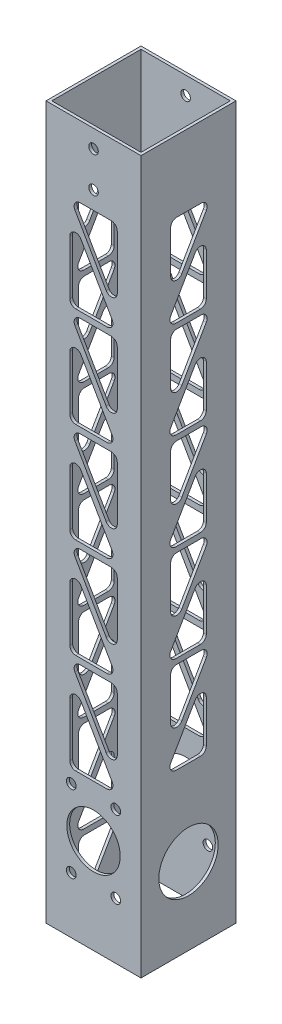
SolidWorks part; units mm, degrees
material "6061 Alloy"
ref_plane "Front Plane" through (0, 0, 0) normal (0, 0, 1) x (1, 0, 0)
ref_plane "Top Plane" through (0, 0, 0) normal (0, 1, 0) x (1, 0, 0)
ref_plane "Right Plane" through (0, 0, 0) normal (1, 0, 0) x (0, 0, -1)
sketch "Sketch1" plane through (0, 0, 0) normal (0, 1, 0) x (1, 0, 0)
  line L1 (25.4, 25.4) -> (-25.4, 25.4)
  line L2 (25.4, 25.4) -> (25.4, -25.4)
  line L3 (25.4, -25.4) -> (-25.4, -25.4)
  line L4 (-25.4, 25.4) -> (-25.4, -25.4)
  line L5 (25.4, 25.4) -> (-25.4, -25.4) construction
  line L6 (25.4, -25.4) -> (-25.4, 25.4) construction
  point P0 (0, 0)
  dimension "D1" = 50.8
extrude "Extrude-Thin1" add sketch "Sketch1" along normal blind 381 thin thin type one direction reverse wall 1.524
sketch "Sketch2" plane through (0, 0, 0) normal (0, 0, 1) x (1, 0, 0)
  line L0 (-36.2563, 68.2625) -> (38.5702, 68.2625) construction
  line L1 (-25.4, 0) -> (25.4, 0) construction
  line L2 (-25.4, 50.8) -> (25.4, 50.8) construction
  line L6 (25.4, 381) -> (25.4, 0) construction
  line L7 (-25.4, 381) -> (-25.4, 0) construction
  line L8 (-11.9062, 30.1778) -> (11.9063, 30.1778) construction
  line L9 (-11.9062, 71.4222) -> (11.9063, 71.4222) construction
  circle A0 centre (0, 50.8) radius 14.3002
  circle A1 centre (0, 50.8) radius 23.8125 construction
  circle A2 centre (-11.9062, 30.1778) radius 2.5908
  circle A3 centre (11.9063, 30.1778) radius 2.5908
  circle A4 centre (11.9063, 71.4222) radius 2.5908
  circle A5 centre (-11.9062, 71.4222) radius 2.5908
  point P11 (0, 50.8)
  dimension "D1" = 28.6004
  dimension "D3" = 17.4625
  dimension "D4" = 47.625
  dimension "D6" = 5.1816
  dimension "D2" = 50.8
  dimension "D5" = 60
extrude "Cut-Extrude1" cut sketch "Sketch2" along normal through all both and the other way through all
sketch "Sketch3" plane through (25.4, 0, 0) normal (1, 0, 0) x (0, 0, -1)
  line L0 (-25.4, 50.8) -> (25.4, 50.8) construction
  line L1 (-25.4, 65.1002) -> (-25.4, 36.4998) construction
  line L3 (25.4, 381) -> (25.4, 0) construction
  circle A0 centre (0, 41.275) radius 15.875
  point P9 (0, 50.8)
  dimension "D1" = 31.75
  dimension "D2" = 9.525
extrude "Cut-Extrude2" cut sketch "Sketch3" against normal up to surface (1.524 mm away) up to face at (23.876, 190.5, 0)
sketch "Sketch4" plane through (0, 0, 25.4) normal (0, 0, 1) x (1, 0, 0)
  line L0 (-25.4, 381) -> (25.4, 381) construction
  circle A0 centre (0, 371.475) radius 2.54
  circle A1 centre (0, 352.425) radius 2.54
  dimension "D1" = 5.08
  dimension "D2" = 9.525
  dimension "D3" = 28.575
hole_wizard "#10 Clearance Hole1" positions "Sketch5" profile "Sketch6" hole size "#10" standard "ANSI Inch" end condition through all
sketch "Sketch5" plane through (0, 0, 25.4) normal (0, 0, 1) x (1, 0, 0)
  point P0 (0, 352.425)
  point P3 (0, 371.475)
sketch "Sketch6" plane through (0, 352.425, 25.4) normal (1, 0, 0) x (0, -1, 0)
  line L0 (0, 0) -> (0, 50.8)
  line L1 (0, 50.8) -> (2.5527, 50.8)
  line L2 (2.5527, 50.8) -> (2.5527, 0)
  line L5 (2.5527, 0) -> (0, 0)
  line L11 (0, -6.35) -> (0, 107.95) construction
  dimension "Thru Hole Dia." = 5.1054
  dimension "Thru Hole Depth" = 50.8
sketch "Sketch7" plane through (0, 0, 25.4) normal (0, 0, 1) x (1, 0, 0)
  line L0 (-12.7, 381) -> (-12.7, 0) construction
  line L1 (12.7, 381) -> (12.7, 0) construction
  line L2 (-12.7, 0) -> (-25.4, 0) construction
  line L3 (-25.4, 0) -> (25.4, 0) construction
  line L4 (-25.4, 381) -> (-25.4, 0) construction
  line L5 (12.7, 0) -> (25.4, 0) construction
  line L6 (-25.4, 381) -> (25.4, 381) construction
  line L7 (-12.7, 342.9) -> (12.7, 342.9) construction
  line L8 (-12.7, 79.375) -> (12.7, 79.375) construction
  line L9 (-7.2007, 342.9) -> (9.525, 342.9)
  line L10 (12.7, 339.725) -> (12.7, 310.7552)
  line L11 (6.7754, 309.1677) -> (-9.9504, 338.1375)
  line L12 (-9.525, 292.5559) -> (7.2007, 292.5559)
  line L13 (-12.7, 295.7309) -> (-12.7, 324.7007)
  line L14 (-6.7754, 326.2882) -> (9.9504, 297.3184)
  line L15 (-0.1024, 314.7303) -> (2.6473, 316.3178) construction
  line L16 (-7.2007, 289.3809) -> (9.525, 289.3809)
  line L17 (12.7, 286.2059) -> (12.7, 257.2361)
  line L18 (6.7754, 255.6486) -> (-9.9504, 284.6184)
  line L19 (-12.7, 242.2118) -> (-12.7, 271.1816)
  line L20 (-9.525, 239.0368) -> (7.2007, 239.0368)
  line L21 (-6.7754, 272.7691) -> (9.9504, 243.7993)
  line L34 (-7.2007, 342.9) -> (-7.2007, 289.3809) construction
  line L35 (-7.2007, 235.8618) -> (9.525, 235.8618)
  line L36 (12.7, 232.6868) -> (12.7, 203.717)
  line L37 (6.7754, 202.1295) -> (-9.9504, 231.0993)
  line L38 (-12.7, 188.6927) -> (-12.7, 217.6626)
  line L39 (-9.525, 185.5177) -> (7.2007, 185.5177)
  line L40 (-6.7754, 219.2501) -> (9.9504, 190.2802)
  line L41 (-7.2007, 182.3427) -> (9.525, 182.3427)
  line L42 (12.7, 179.1677) -> (12.7, 150.1979)
  line L43 (6.7754, 148.6104) -> (-9.9504, 177.5802)
  line L44 (-12.7, 135.1736) -> (-12.7, 164.1435)
  line L45 (-9.525, 131.9986) -> (7.2007, 131.9986)
  line L46 (-6.7754, 165.731) -> (9.9504, 136.7611)
  line L47 (-7.2007, 128.8236) -> (9.525, 128.8236)
  line L48 (12.7, 125.6486) -> (12.7, 96.6788)
  line L49 (6.7754, 95.0913) -> (-9.9504, 124.0611)
  line L50 (-12.7, 81.6545) -> (-12.7, 110.6244)
  line L51 (-9.525, 78.4795) -> (7.2007, 78.4795)
  line L52 (-6.7754, 112.2119) -> (9.9504, 83.242)
  arc A0 (-9.9504, 338.1375) -> (-7.2007, 342.9) centre (-7.2007, 339.725) cw
  arc A1 (9.525, 342.9) -> (12.7, 339.725) centre (9.525, 339.725) cw
  arc A2 (12.7, 310.7552) -> (6.7754, 309.1677) centre (9.525, 310.7552) cw
  arc A3 (9.9504, 297.3184) -> (7.2007, 292.5559) centre (7.2007, 295.7309) cw
  arc A4 (-12.7, 324.7007) -> (-6.7754, 326.2882) centre (-9.525, 324.7007) cw
  arc A5 (-12.7, 295.7309) -> (-9.525, 292.5559) centre (-9.525, 295.7309) ccw
  arc A6 (12.7, 257.2361) -> (6.7754, 255.6486) centre (9.525, 257.2361) cw
  arc A7 (-9.9504, 284.6184) -> (-7.2007, 289.3809) centre (-7.2007, 286.2059) cw
  arc A8 (9.525, 289.3809) -> (12.7, 286.2059) centre (9.525, 286.2059) cw
  arc A9 (-12.7, 271.1816) -> (-6.7754, 272.7691) centre (-9.525, 271.1816) cw
  arc A10 (-12.7, 242.2118) -> (-9.525, 239.0368) centre (-9.525, 242.2118) ccw
  arc A11 (9.9504, 243.7993) -> (7.2007, 239.0368) centre (7.2007, 242.2118) cw
  arc A12 (12.7, 203.717) -> (6.7754, 202.1295) centre (9.525, 203.717) cw
  arc A13 (-9.9504, 231.0993) -> (-7.2007, 235.8618) centre (-7.2007, 232.6868) cw
  arc A14 (9.525, 235.8618) -> (12.7, 232.6868) centre (9.525, 232.6868) cw
  arc A15 (-12.7, 217.6626) -> (-6.7754, 219.2501) centre (-9.525, 217.6626) cw
  arc A16 (-12.7, 188.6927) -> (-9.525, 185.5177) centre (-9.525, 188.6927) ccw
  arc A17 (9.9504, 190.2802) -> (7.2007, 185.5177) centre (7.2007, 188.6927) cw
  arc A18 (12.7, 150.1979) -> (6.7754, 148.6104) centre (9.525, 150.1979) cw
  arc A19 (-9.9504, 177.5802) -> (-7.2007, 182.3427) centre (-7.2007, 179.1677) cw
  arc A20 (9.525, 182.3427) -> (12.7, 179.1677) centre (9.525, 179.1677) cw
  arc A21 (-12.7, 164.1435) -> (-6.7754, 165.731) centre (-9.525, 164.1435) cw
  arc A22 (-12.7, 135.1736) -> (-9.525, 131.9986) centre (-9.525, 135.1736) ccw
  arc A23 (9.9504, 136.7611) -> (7.2007, 131.9986) centre (7.2007, 135.1736) cw
  arc A24 (12.7, 96.6788) -> (6.7754, 95.0913) centre (9.525, 96.6788) cw
  arc A25 (-9.9504, 124.0611) -> (-7.2007, 128.8236) centre (-7.2007, 125.6486) cw
  arc A26 (9.525, 128.8236) -> (12.7, 125.6486) centre (9.525, 125.6486) cw
  arc A27 (-12.7, 110.6244) -> (-6.7754, 112.2119) centre (-9.525, 110.6244) cw
  arc A28 (-12.7, 81.6545) -> (-9.525, 78.4795) centre (-9.525, 81.6545) ccw
  arc A29 (9.9504, 83.242) -> (7.2007, 78.4795) centre (7.2007, 81.6545) cw
  point P31 (12.7, 298.9059)
  point P34 (12.7, 292.5559)
  point P37 (-12.7, 336.55)
  point P40 (-12.7, 292.5559)
  dimension "D5" = 3.175
  dimension "D1" = 12.7
  dimension "D2" = 38.1
  dimension "D3" = 79.375
  dimension "D4" = 30
  dimension "D7" = 3.175
  dimension "D8" = 3.175
  dimension "D6" = 5
extrude "Cut-Extrude3" cut sketch "Sketch7" against normal through all
sketch "Sketch8" plane through (-25.4, 0, 0) normal (-1, 0, 0) x (0, 0, 1)
  line L0 (-12.2746, 342.9) -> (9.525, 342.9) construction
  line L1 (-6.7754, 342.9) -> (6.35, 342.9)
  line L2 (9.525, 339.725) -> (9.525, 316.9912)
  line L3 (3.6004, 315.4037) -> (-9.525, 338.1375)
  line L4 (-6.35, 294.0294) -> (6.7754, 294.0294)
  line L5 (-9.525, 297.2044) -> (-9.525, 319.9382)
  line L6 (-3.6004, 321.5257) -> (9.525, 298.7919)
  line L7 (4.3689, 307.7225) -> (7.1185, 309.31) construction
  line L8 (-9.525, 381) -> (-9.525, 0) construction
  line L9 (-25.4, 0) -> (25.4, 0) construction
  line L10 (9.525, 0) -> (9.525, 381) construction
  line L11 (-25.4, 381) -> (25.4, 381) construction
  line L12 (-9.525, 392.3126) -> (-25.4, 392.3126) construction
  line L13 (-25.4, 381) -> (-25.4, 0) construction
  line L14 (9.525, 392.3126) -> (25.4, 392.3126) construction
  line L15 (25.4, 381) -> (25.4, 0) construction
  line L16 (-6.35, 242.2379) -> (6.7754, 242.2379)
  line L17 (-9.525, 245.4129) -> (-9.525, 268.1467)
  line L18 (-3.6004, 269.7342) -> (9.525, 247.0004)
  line L19 (9.525, 287.9334) -> (9.525, 265.1996)
  line L20 (3.6004, 263.6121) -> (-9.525, 286.3459)
  line L21 (-6.7754, 291.1084) -> (6.35, 291.1084)
  line L22 (-6.35, 190.4463) -> (6.7754, 190.4463)
  line L23 (-9.525, 193.6213) -> (-9.525, 216.3551)
  line L24 (-3.6004, 217.9426) -> (9.525, 195.2088)
  line L25 (9.525, 236.1419) -> (9.525, 213.4081)
  line L26 (3.6004, 211.8206) -> (-9.525, 234.5544)
  line L27 (-6.7754, 239.3169) -> (6.35, 239.3169)
  line L28 (-6.35, 138.6547) -> (6.7754, 138.6547)
  line L29 (-9.525, 141.8297) -> (-9.525, 164.5635)
  line L30 (-3.6004, 166.151) -> (9.525, 143.4172)
  line L31 (9.525, 184.3503) -> (9.525, 161.6165)
  line L32 (3.6004, 160.029) -> (-9.525, 182.7628)
  line L33 (-6.7754, 187.5253) -> (6.35, 187.5253)
  line L34 (-25.4, 87.3125) -> (25.4, 87.3125) construction
  line L35 (-6.35, 86.8632) -> (6.7754, 86.8632)
  line L36 (-9.525, 90.0382) -> (-9.525, 112.772)
  line L37 (-3.6004, 114.3595) -> (9.525, 91.6257)
  line L38 (9.525, 132.5587) -> (9.525, 109.8249)
  line L39 (3.6004, 108.2374) -> (-9.525, 130.9712)
  line L40 (-6.7754, 135.7337) -> (6.35, 135.7337)
  line L41 (-6.35, 35.0716) -> (6.7754, 35.0716)
  line L42 (-9.525, 38.2466) -> (-9.525, 60.9804)
  line L43 (-3.6004, 62.5679) -> (9.525, 39.8341)
  line L44 (9.525, 80.7672) -> (9.525, 58.0334)
  line L45 (3.6004, 56.4459) -> (-9.525, 79.1797)
  line L46 (-6.7754, 83.9422) -> (6.35, 83.9422)
  line L50 (9.525, 28.9756) -> (9.525, 6.2418)
  line L51 (3.6004, 4.6543) -> (-9.525, 27.3881)
  line L52 (-6.7754, 32.1506) -> (6.35, 32.1506)
  line L53 (-6.35, -16.7199) -> (6.7754, -16.7199) [skipped]
  line L54 (-3.6004, 10.7764) -> (9.525, -11.9574) [skipped]
  line L55 (-9.525, -13.5449) -> (-9.525, 9.1889) [skipped]
  arc A0 (-9.525, 338.1375) -> (-6.7754, 342.9) centre (-6.7754, 339.725) cw
  arc A1 (6.35, 342.9) -> (9.525, 339.725) centre (6.35, 339.725) cw
  arc A2 (9.525, 316.9912) -> (3.6004, 315.4037) centre (6.35, 316.9912) cw
  arc A3 (9.525, 298.7919) -> (6.7754, 294.0294) centre (6.7754, 297.2044) cw
  arc A4 (-9.525, 319.9382) -> (-3.6004, 321.5257) centre (-6.35, 319.9382) cw
  arc A5 (-9.525, 297.2044) -> (-6.35, 294.0294) centre (-6.35, 297.2044) ccw
  arc A6 (-9.525, 245.4129) -> (-6.35, 242.2379) centre (-6.35, 245.4129) ccw
  arc A7 (-9.525, 268.1467) -> (-3.6004, 269.7342) centre (-6.35, 268.1467) cw
  arc A8 (9.525, 247.0004) -> (6.7754, 242.2379) centre (6.7754, 245.4129) cw
  arc A9 (9.525, 265.1996) -> (3.6004, 263.6121) centre (6.35, 265.1996) cw
  arc A10 (6.35, 291.1084) -> (9.525, 287.9334) centre (6.35, 287.9334) cw
  arc A11 (-9.525, 286.3459) -> (-6.7754, 291.1084) centre (-6.7754, 287.9334) cw
  arc A12 (-9.525, 193.6213) -> (-6.35, 190.4463) centre (-6.35, 193.6213) ccw
  arc A13 (-9.525, 216.3551) -> (-3.6004, 217.9426) centre (-6.35, 216.3551) cw
  arc A14 (9.525, 195.2088) -> (6.7754, 190.4463) centre (6.7754, 193.6213) cw
  arc A15 (9.525, 213.4081) -> (3.6004, 211.8206) centre (6.35, 213.4081) cw
  arc A16 (6.35, 239.3169) -> (9.525, 236.1419) centre (6.35, 236.1419) cw
  arc A17 (-9.525, 234.5544) -> (-6.7754, 239.3169) centre (-6.7754, 236.1419) cw
  arc A18 (-9.525, 141.8297) -> (-6.35, 138.6547) centre (-6.35, 141.8297) ccw
  arc A19 (-9.525, 164.5635) -> (-3.6004, 166.151) centre (-6.35, 164.5635) cw
  arc A20 (9.525, 143.4172) -> (6.7754, 138.6547) centre (6.7754, 141.8297) cw
  arc A21 (9.525, 161.6165) -> (3.6004, 160.029) centre (6.35, 161.6165) cw
  arc A22 (6.35, 187.5253) -> (9.525, 184.3503) centre (6.35, 184.3503) cw
  arc A23 (-9.525, 182.7628) -> (-6.7754, 187.5253) centre (-6.7754, 184.3503) cw
  arc A24 (-9.525, 90.0382) -> (-6.35, 86.8632) centre (-6.35, 90.0382) ccw
  arc A25 (-9.525, 112.772) -> (-3.6004, 114.3595) centre (-6.35, 112.772) cw
  arc A26 (9.525, 91.6257) -> (6.7754, 86.8632) centre (6.7754, 90.0382) cw
  arc A27 (9.525, 109.8249) -> (3.6004, 108.2374) centre (6.35, 109.8249) cw
  arc A28 (6.35, 135.7337) -> (9.525, 132.5587) centre (6.35, 132.5587) cw
  arc A29 (-9.525, 130.9712) -> (-6.7754, 135.7337) centre (-6.7754, 132.5587) cw
  arc A30 (-9.525, 38.2466) -> (-6.35, 35.0716) centre (-6.35, 38.2466) ccw
  arc A31 (-9.525, 60.9804) -> (-3.6004, 62.5679) centre (-6.35, 60.9804) cw
  arc A32 (9.525, 39.8341) -> (6.7754, 35.0716) centre (6.7754, 38.2466) cw
  arc A33 (9.525, 58.0334) -> (3.6004, 56.4459) centre (6.35, 58.0334) cw
  arc A34 (6.35, 83.9422) -> (9.525, 80.7672) centre (6.35, 80.7672) cw
  arc A35 (-9.525, 79.1797) -> (-6.7754, 83.9422) centre (-6.7754, 80.7672) cw
  arc A39 (9.525, 6.2418) -> (3.6004, 4.6543) centre (6.35, 6.2418) cw
  arc A40 (6.35, 32.1506) -> (9.525, 28.9756) centre (6.35, 28.9756) cw
  arc A41 (-9.525, 27.3881) -> (-6.7754, 32.1506) centre (-6.7754, 28.9756) cw
  arc A42 (9.525, -11.9574) -> (6.7754, -16.7199) centre (6.7754, -13.5449) cw [skipped]
  arc A43 (-9.525, 9.1889) -> (-3.6004, 10.7764) centre (-6.35, 9.1889) cw [skipped]
  arc A44 (-9.525, -13.5449) -> (-6.35, -16.7199) centre (-6.35, -13.5449) ccw [skipped]
  point P150 (7.1718, 3.175)
  dimension "D2" = 3.175
  dimension "D1" = 30
  dimension "D3" = 38.1
  dimension "D4" = 15.875
  dimension "D5" = 3.175
  dimension "D7" = 3.175
  dimension "D8" = 87.3125
  dimension "D6" = 7
extrude "Cut-Extrude4" cut sketch "Sketch8" against normal through all contours A14 L24 A13 L23 A12 L22 | A17 L26 A15 L25 A16 L27 | A8 L18 A7 L17 A6 L16 | A11 L20 A9 L19 A10 L21 | L5 A5 L4 A3 L6 A4 | A2 L2 A1 L1 A0 L3 | A23 L32 A21 L31 A22 L33 | A20 L30 A19 L29 A18 L28 | A29 L39 A27 L38 A28 L40 | A26 L37 A25 L36 A24 L35 region at (-25.4, 331.265, 2.0868) region at (-25.4, 305.6645, -2.0868) region at (-25.4, 253.8729, -2.0868) region at (-25.4, 279.4734, 2.0868) region at (-25.4, 202.0813, -2.0868) region at (-25.4, 227.6819, 2.0868) region at (-25.4, 150.2898, -2.0868) region at (-25.4, 175.8903, 2.0868) region at (-25.4, 98.4982, -2.0868) region at (-25.4, 124.0987, 2.0868)
extrude "Cut-Extrude5" cut sketch "Sketch8<4>" against normal up to next contours A41 L51 A39 L50 A40 L52 | A32 L43 A31 L42 A30 L41 | A35 L45 A33 L44 A34 L46 region at (-25.4, 46.7066, -2.0868) region at (-25.4, 72.3072, 2.0868) region at (-25.4, 20.5156, 2.0868)
sketch "Sketch8<4>" plane through (-25.4, 0, 0) normal (-1, 0, 0) x (0, 0, 1) same geometry as "Sketch8"
